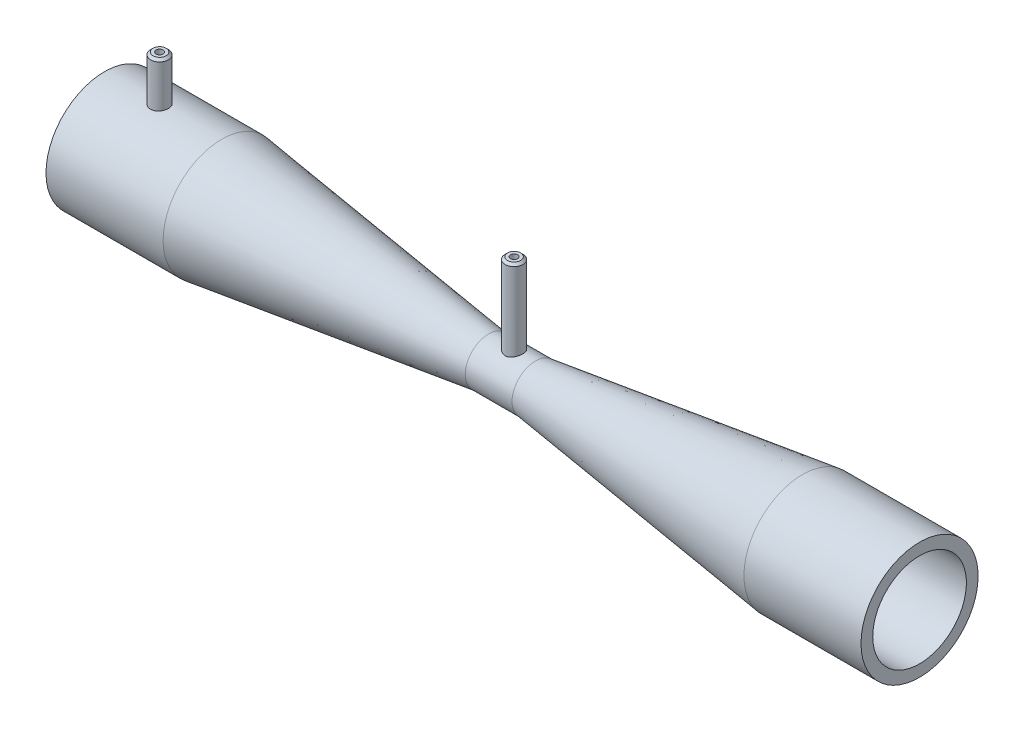
SolidWorks part; units mm, degrees
ref_plane "Front Plane" through (0, 0, 0) normal (0, 0, 1) x (1, 0, 0)
ref_plane "Top Plane" through (0, 0, 0) normal (0, 1, 0) x (1, 0, 0)
ref_plane "Right Plane" through (0, 0, 0) normal (1, 0, 0) x (0, 0, -1)
sketch "Sketch6" plane through (0, 0, 0) normal (0, 0, 1) x (1, 0, 0)
  line L0 (0, 0) -> (174, 0) construction
  line L1 (0.5611, 12.5) -> (25.5611, 12.5)
  line L2 (25.5611, 12.5) -> (82.5611, 5)
  line L3 (82.5611, 5) -> (92.5611, 5)
  line L4 (149.5611, 12.5) -> (92.5611, 5)
  line L5 (149.5611, 12.5) -> (174.5611, 12.5)
  line L6 (0.5611, 10) -> (25.3973, 10)
  line L7 (25.3973, 10) -> (82.3973, 2.5)
  line L8 (82.3973, 2.5) -> (92.7248, 2.5)
  line L9 (149.7248, 10) -> (92.7248, 2.5)
  line L10 (149.7248, 10) -> (174.5611, 10)
  line L11 (0.5611, 12.5) -> (0.5611, 10)
  line L12 (174.5611, 12.5) -> (174.5611, 10)
  dimension "D1" = 174
  dimension "D2" = 25
  dimension "D3" = 12.5
  dimension "D4" = 57
  dimension "D5" = 5
  dimension "D6" = 10
  dimension "D7" = 57
  dimension "D8" = 25
  dimension "D9" = 12.5
  dimension "D10" = 2.5
revolve "Revolve1" add sketch "Sketch6" angle 360 about L0
ref_plane "Plane1" through (0, 22, 0) normal (0, 1, 0) x (1, 0, 0)
sketch "Sketch14" plane through (0, 22, 0) normal (0, 1, 0) x (1, 0, 0)
  line L0 (0.5611, 0) -> (87.9966, 0)
  line L2 (0.5611, 12.5) -> (0.5611, -12.5) construction
  circle A0 centre (12.3034, 0) radius 1.9
  circle A1 centre (87.9966, 0) radius 1.9
  dimension "D1" = 3.8
  dimension "D2" = 3.8
extrude "Boss-Extrude7" add sketch "Sketch14" against normal up to body contours A1 | A0 region at (87.9966, 22, -1.8463)
sketch "Sketch15" plane through (0, 22, 0) normal (0, 1, 0) x (1, 0, 0)
  circle A0 centre (12.3034, 0) radius 0.75
  circle A1 centre (87.9966, 0) radius 0.75
  dimension "D1" = 1.5
  dimension "D2" = 1.5
extrude "Cut-Extrude6" cut sketch "Sketch15" against normal blind 19.75
chamfer "Chamfer2" distance 0.5 angle 45 2 edges at (12.3034, 22, 1.9) (87.9966, 22, 1.9)
fillet "Fillet3" radius 1 2 edges at (87.8604, 2.3887, -0.7375) (12.1333, 9.9733, -0.7304)
